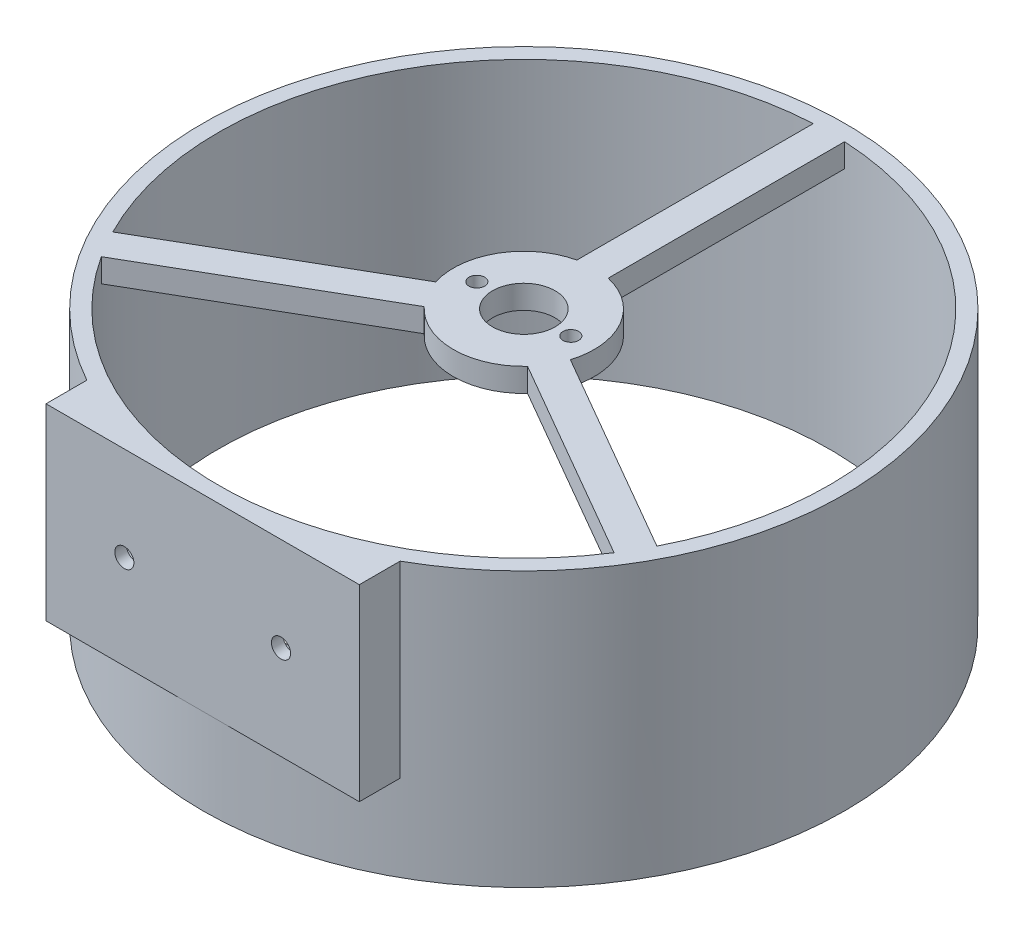
SolidWorks part; units mm, degrees
ref_plane "前视基准面" through (0, 0, 0) normal (0, 0, 1) x (1, 0, 0)
ref_plane "上视基准面" through (0, 0, 0) normal (0, 1, 0) x (1, 0, 0)
ref_plane "右视基准面" through (0, 0, 0) normal (1, 0, 0) x (0, 0, -1)
sketch "草图1" plane through (0, 0, 0) normal (0, 1, 0) x (1, 0, 0)
  circle A0 centre (0, 0) radius 39
  circle A1 centre (0, 0) radius 41
  dimension "D1" = 78
  dimension "D2" = 2
extrude "凸台-拉伸1" add sketch "草图1" along normal blind 20
sketch "草图2" plane through (0, 20, 0) normal (0, 1, 0) x (1, 0, 0)
  line L0 (20, -41) -> (-20, -41)
  line L1 (-20, -41) -> (-20, -35.7911)
  line L2 (0, -41) -> (0, -31.4417) construction
  line L3 (20, -41) -> (20, -35.7911)
  circle A0 centre (0, 0) radius 41 construction
  arc A1 (-20, -35.7911) -> (20, -35.7911) centre (0, 0) ccw
  circle M5 centre (0, 0) radius 41
extrude "凸台-拉伸2" add sketch "草图2" against normal blind 14 contours L1 L0 M5 | L0 L3 M5 region at (15.0657, 20, 39.4559) region at (-15.0657, 20, 39.4559)
sketch "草图3" plane through (0, 20, 0) normal (0, 1, 0) x (1, 0, 0)
  line L0 (-2, 38.9487) -> (-2, 8.775)
  line L1 (0, 39) -> (0, 9) construction
  line L2 (2, 38.9487) -> (2, 8.775)
  line L3 (34.7305, -17.7423) -> (8.5993, -2.6554)
  line L4 (32.7305, -21.2064) -> (6.5993, -6.1195)
  line L5 (-32.7305, -21.2064) -> (-6.5993, -6.1195)
  line L6 (-34.7305, -17.7423) -> (-8.5993, -2.6554)
  circle A0 centre (0, 0) radius 4
  circle A1 centre (-6, 0) radius 1
  circle A2 centre (6, 0) radius 1
  arc A3 (-6.5993, -6.1195) -> (6.5993, -6.1195) centre (0, 0) ccw
  circle A4 centre (0, 0) radius 39 construction
  arc A5 (2, 38.9487) -> (-2, 38.9487) centre (0, 0) ccw
  arc A6 (32.7305, -21.2064) -> (34.7305, -17.7423) centre (0, 0) ccw
  arc A7 (-34.7305, -17.7423) -> (-32.7305, -21.2064) centre (0, 0) ccw
  arc A8 (-2, 8.775) -> (-8.5993, -2.6554) centre (0, 0) ccw
  arc A9 (8.5993, -2.6554) -> (2, 8.775) centre (0, 0) ccw
  point P28 (0, 0)
  dimension "D1" = 8
  dimension "D2" = 2
  dimension "D3" = 6
  dimension "D4" = 2
  dimension "D5" = 6
  dimension "D6" = 18
  dimension "D7" = 2
  dimension "D8" = 3
extrude "凸台-拉伸3" add sketch "草图3" against normal blind 3
sketch "草图4" plane through (0, 0, 41) normal (0, 0, 1) x (1, 0, 0)
  line L0 (20, 20) -> (-20, 20) construction
  line L1 (-10, 4.7668) -> (-7.2, 6.3834)
  line L2 (-7.2, 6.3834) -> (-7.2, 9.6166)
  line L3 (-7.2, 9.6166) -> (-10, 11.2332)
  line L4 (-10, 11.2332) -> (-12.8, 9.6166)
  line L5 (-12.8, 9.6166) -> (-12.8, 6.3834)
  line L6 (-12.8, 6.3834) -> (-10, 4.7668)
  line L7 (0, 0) -> (0, -4.0742) construction
  line L8 (12.8, 6.3834) -> (10, 4.7668)
  line L9 (12.8, 9.6166) -> (12.8, 6.3834)
  line L10 (10, 11.2332) -> (12.8, 9.6166)
  line L11 (7.2, 9.6166) -> (10, 11.2332)
  line L12 (7.2, 6.3834) -> (7.2, 9.6166)
  line L13 (10, 4.7668) -> (7.2, 6.3834)
  circle A0 centre (-10, 8) radius 2.8 construction
  dimension "D1" = 5.6
  dimension "D2" = 10
  dimension "D3" = 12
sketch "草图7" plane through (0, 6, 0) normal (0, -1, 0) x (1, 0, 0)
  line L2 (-20, 41) -> (-20, 35.7911)
  line L3 (0, 41) -> (-20, 41)
  line L4 (-20, 41) -> (-20, 35.7911)
  line L5 (0, 41) -> (-20, 41)
  line L6 (20, 41) -> (0, 41)
  line L7 (20, 35.7911) -> (20, 41)
  line L8 (20, 41) -> (0, 41)
  line L9 (20, 35.7911) -> (20, 41)
  arc A1 (0, 41) -> (-20, 35.7911) centre (0, 0) ccw
  arc A2 (0, 41) -> (-20, 35.7911) centre (0, 0) ccw
  arc A3 (20, 35.7911) -> (0, 41) centre (0, 0) ccw
  arc A4 (20, 35.7911) -> (0, 41) centre (0, 0) ccw
  line M7 (-20, 41) -> (-20, 35.7911)
  arc M8 (-20, 35.7911) -> (0, 41) centre (0, 0) cw
  line M9 (0, 41) -> (-20, 41)
  dimension "D1" = 0
  dimension "D2" = 0
extrude "切除-拉伸3" cut sketch "草图7" against normal blind 3 contours M9 M7 M8 | A4 L9 L8 region at (-15.0657, 6, 39.4559) region at (15.0657, 6, 39.4559)
sketch "草图9" plane through (0, 0, 0) normal (0, -1, 0) x (1, 0, 0)
sketch "草图10" plane through (0, 0, 0) normal (0, -1, 0) x (1, 0, 0)
sketch "草图11" plane through (0, 0, 0) normal (0, -1, 0) x (1, 0, 0)
sketch "草图12" plane through (0, 0, 0) normal (0, -1, 0) x (1, 0, 0)
  circle A2 centre (0.1979, 0.0085) radius 41.1981
extrude "凸台-拉伸5" add sketch "草图1<2>" along normal blind 10 and the other way blind 15
sketch "草图1<2>" plane through (0, 0, 0) normal (0, 1, 0) x (1, 0, 0) same geometry as "草图1"
extrude "凸台-拉伸7" add sketch "草图7<4>" along normal blind 10
sketch "草图7<4>" plane through (0, 6, 0) normal (0, -1, 0) x (1, 0, 0) same geometry as "草图7"
extrude "凸台-拉伸8" add sketch "草图7<5>" along normal blind 10 and the other way blind 5 contours M9 M7 M8 | A4 L9 L8 region at (-15.0657, 6, 39.4559) region at (15.0657, 6, 39.4559)
sketch "草图7<5>" plane through (0, 6, 0) normal (0, -1, 0) x (1, 0, 0) same geometry as "草图7"
extrude "切除-拉伸4" cut sketch "草图4" against normal blind 10
extrude "凸台-拉伸9" add sketch "草图4<3>" along normal blind 10 and the other way blind 1.5
sketch "草图4<3>" plane through (0, 0, 41) normal (0, 0, 1) x (1, 0, 0) same geometry as "草图4"
sketch "草图13" plane through (0, 0, 51) normal (0, 0, 1) x (1, 0, 0)
  line L0 (10, 11.2332) -> (7.2, 9.6166)
  line L1 (7.2, 9.6166) -> (7.2, 6.3834)
  line L2 (7.2, 6.3834) -> (10, 4.7668)
  line L3 (10, 4.7668) -> (12.8, 6.3834)
  line L4 (12.8, 6.3834) -> (12.8, 9.6166)
  line L5 (12.8, 9.6166) -> (10, 11.2332)
  line L6 (-10, 11.2332) -> (-12.8, 9.6166)
  line L7 (-12.8, 9.6166) -> (-12.8, 6.3834)
  line L8 (-12.8, 6.3834) -> (-10, 4.7668)
  line L9 (-10, 4.7668) -> (-7.2, 6.3834)
  line L10 (-7.2, 6.3834) -> (-7.2, 9.6166)
  line L11 (-7.2, 9.6166) -> (-10, 11.2332)
extrude "切除-拉伸6" cut sketch "草图13" against normal blind 10
sketch "草图16" plane through (0, 0, 41) normal (0, 0, 1) x (1, 0, 0)
  line L1 (0, 0) -> (0, 20) construction
  line L2 (20, 20) -> (-20, 20) construction
  line L3 (20, 20) -> (-20, 20) construction
  circle A0 centre (-10, 8) radius 1.22
  circle A1 centre (10, 8) radius 1.22
  point P6 (0, 0)
  dimension "D1" = 20
  dimension "D2" = 10
  dimension "D3" = 12
extrude "切除-拉伸7" cut sketch "草图16" against normal blind 3
